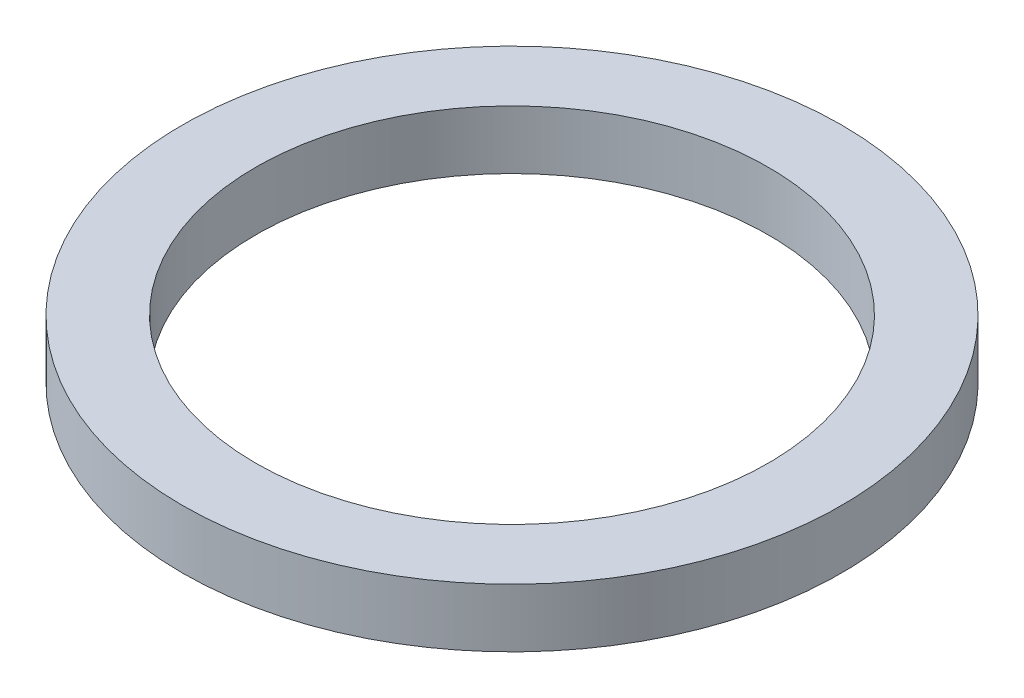
SolidWorks part; units mm, degrees
ref_plane "Front Plane" through (0, 0, 0) normal (0, 0, 1) x (1, 0, 0)
ref_plane "Top Plane" through (0, 0, 0) normal (0, 1, 0) x (1, 0, 0)
ref_plane "Right Plane" through (0, 0, 0) normal (1, 0, 0) x (0, 0, -1)
sketch "Sketch1" plane through (0, 0, 0) normal (0, 1, 0) x (1, 0, 0)
  circle A0 centre (0, 0) radius 45
  dimension "FLANGE_OD" = 90
extrude "Boss-Extrude1" add sketch "Sketch1" along normal blind 8
sketch "Sketch2" plane through (0, 0, 0) normal (0, 1, 0) x (1, 0, 0)
  circle A0 centre (0, 0) radius 35
  dimension "BORE_D" = 70
extrude "Cut-Extrude1" cut sketch "Sketch2" along normal through all
sketch "Sketch3" plane through (0, 8, 0) normal (0, 1, 0) x (1, 0, 0)
  circle A0 centre (0, 0) radius 19.5277 construction
  circle A1 centre (-19.5277, 0) radius 1.7464
  dimension "BOLT_D" = 3.4929
  dimension "BOLT_PCD" = 39.0554
extrude "Cut-Extrude2" cut sketch "Sketch3" against normal blind 7.4203 rebuild error yes
pattern_circular "CirPattern1" count 4 over 360 rebuild error yes
